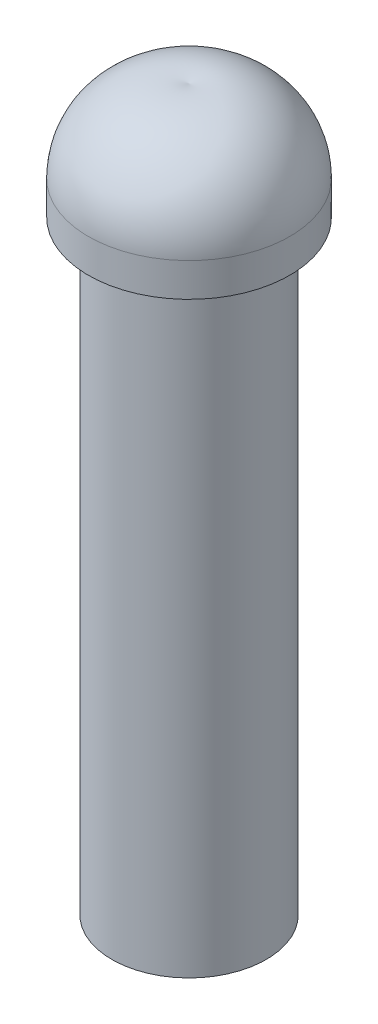
SolidWorks part; units mm, degrees
ref_plane "Přední rovina" through (0, 0, 0) normal (0, 0, 1) x (1, 0, 0)
ref_plane "Horní rovina" through (0, 0, 0) normal (0, 1, 0) x (1, 0, 0)
ref_plane "Pravá rovina" through (0, 0, 0) normal (1, 0, 0) x (0, 0, -1)
sketch "Sketch1" plane through (0, 0, 0) normal (0, 0, 1) x (1, 0, 0)
  line L0 (-2.3, 13.1121) -> (-2.3, -4.8879)
  line L1 (-2.3, -4.8879) -> (-1.55, -4.8879)
  line L2 (-1.55, -4.8879) -> (-1.55, 2.2623)
  line L3 (-1.55, 2.2623) -> (0, 2.2623)
  line L6 (-3, 14.1121) -> (-3, 13.1121)
  line L7 (-3, 13.1121) -> (-2.3, 13.1121)
  line L8 (0, 16.5616) -> (0, 2.2623)
  arc A0 (-3, 14.1121) -> (0, 16.5616) centre (-0.5, 14.1121) cw
  dimension "D2" = 2.5
  dimension "D1" = 18
  dimension "D3" = 1.55
  dimension "D4" = 0.75
  dimension "D5" = 1
  dimension "D6" = 3
revolve "Revolve1" add sketch "Sketch1" angle 360 about L8 region at (-1.3047, 8.0869, 0)
